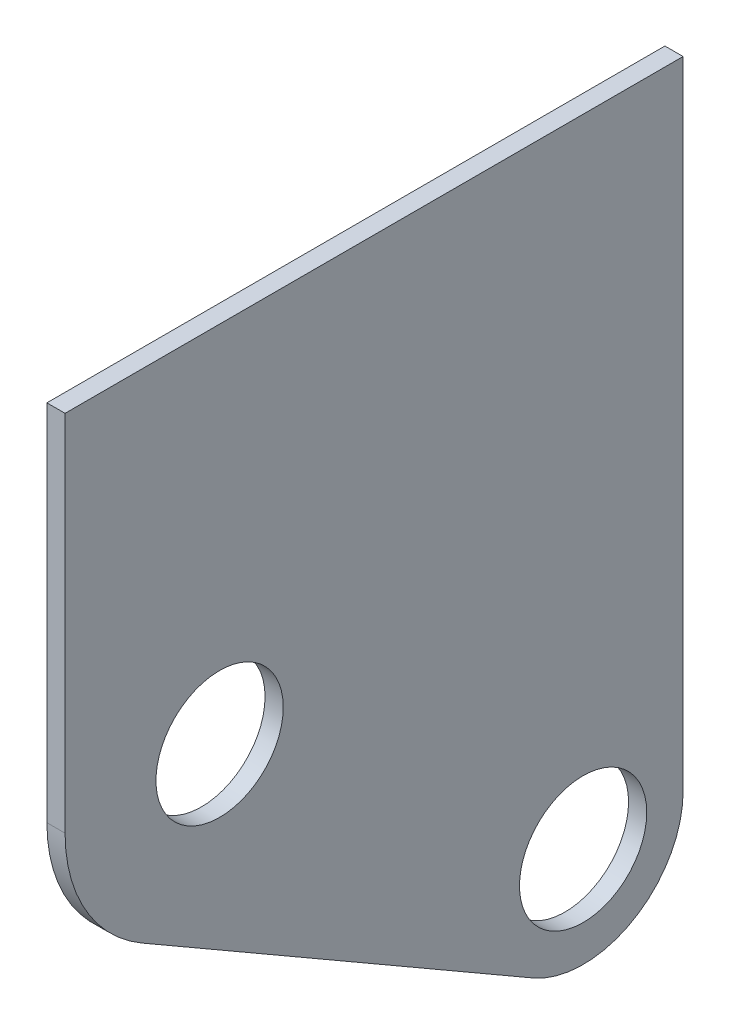
SolidWorks part; units mm, degrees
material "6061-T6 (SS)"
ref_plane "Front" through (0, 0, 0) normal (0, 0, 1) x (1, 0, 0)
ref_plane "Top" through (0, 0, 0) normal (0, 1, 0) x (1, 0, 0)
ref_plane "Right" through (0, 0, 0) normal (1, 0, 0) x (0, 0, -1)
sketch "Sketch2" plane through (0, 0, 0) normal (1, 0, 0) x (0, 0, -1)
  line L0 (53.9658, 0) -> (-53.9658, 0)
  line L1 (-53.9658, 0) -> (-53.9658, -63.5)
  line L2 (-40.472, -86.8719) -> (27.772, -126.2726)
  line L3 (53.9658, -111.1496) -> (53.9658, 0)
  circle A0 centre (-26.9783, -63.5) radius 11.1125
  circle A1 centre (36.5033, -111.1496) radius 11.1125
  circle A2 centre (-26.9783, -63.5) radius 28.575 construction
  circle A3 centre (36.5033, -111.1496) radius 12.7 construction
  arc A4 (-53.9658, -63.5) -> (-40.472, -86.8719) centre (-26.9783, -63.5) ccw
  arc A5 (27.772, -126.2726) -> (53.9658, -111.1496) centre (36.5033, -111.1496) ccw
  point P4 (0, 0)
  dimension "D1" = 22.225
  dimension "D2" = 57.15
  dimension "D3" = 25.4
  dimension "D4" = 38.1
  dimension "D5" = 6.35
  dimension "D6" = 15.875
  dimension "D7" = 120
  dimension "D8" = 63.5
extrude "Boss-Extrude1" add sketch "Sketch2" along normal blind 3.175
